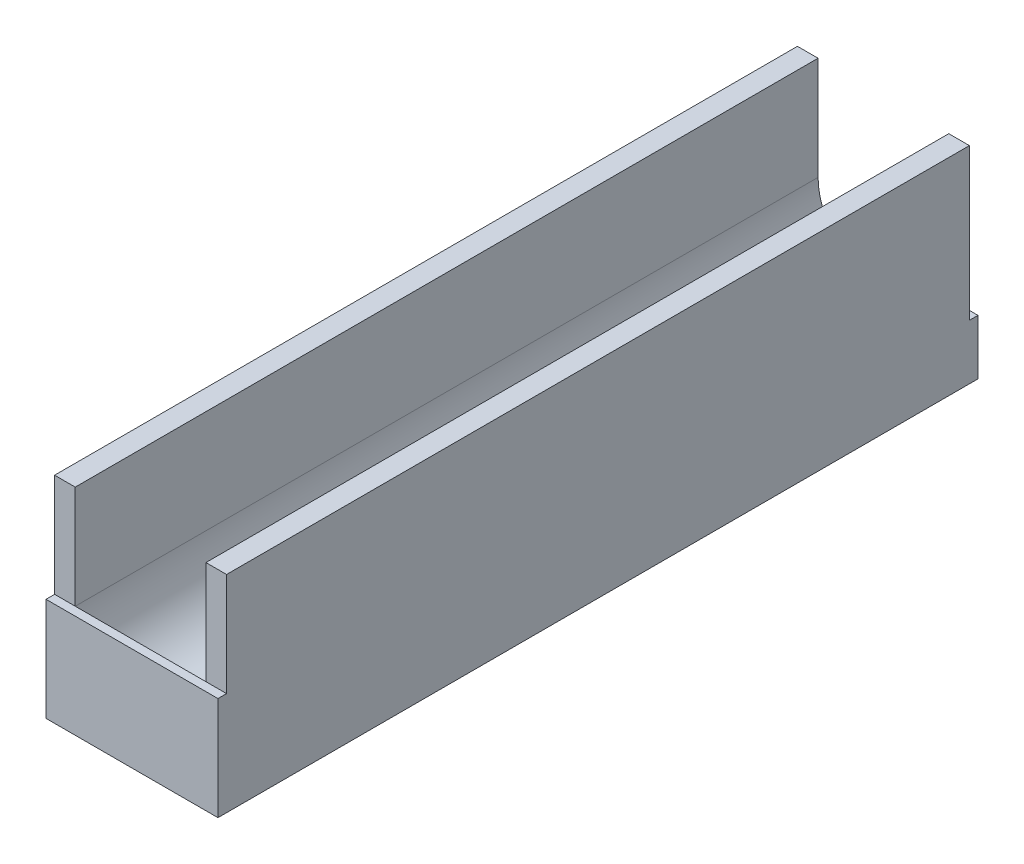
SolidWorks part; units mm, degrees
ref_plane "Front Plane" through (0, 0, 0) normal (0, 0, 1) x (1, 0, 0)
ref_plane "Top Plane" through (0, 0, 0) normal (0, 1, 0) x (1, 0, 0)
ref_plane "Right Plane" through (0, 0, 0) normal (1, 0, 0) x (0, 0, -1)
sketch "Sketch1" plane through (0, 0, 0) normal (0, 0, 1) x (1, 0, 0)
  line L1 (-15.875, 0) -> (15.875, 0)
  line L2 (-15.875, 0) -> (-15.875, 38.1)
  line L3 (-15.875, 38.1) -> (15.875, 38.1)
  line L4 (15.875, 0) -> (15.875, 38.1)
  dimension "D1" = 38.1
  dimension "D2" = 31.75
  dimension "D3" = 15.875
extrude "Boss-Extrude1" add sketch "Sketch1" along normal blind 137.16
sketch "Sketch2" plane through (0, 0, 137.16) normal (0, 0, 1) x (1, 0, 0)
  line L0 (-12.065, 19.05) -> (-12.065, 38.1)
  line L1 (15.875, 38.1) -> (-15.875, 38.1) construction
  line L2 (12.065, 19.05) -> (12.065, 38.1)
  line L3 (12.065, 38.1) -> (-12.065, 38.1)
  arc A2 (-12.065, 19.05) -> (12.065, 19.05) centre (0, 19.05) ccw
  dimension "D1" = 24.13
  dimension "D3" = 19.05
  dimension "D2" = 0
  dimension "D4" = 19.05
extrude "Cut-Extrude1" cut sketch "Sketch2" against normal through all
sketch "Sketch3" plane through (0, 0, 0) normal (0, -1, 0) x (1, 0, 0)
  line L0 (-15.875, 137.16) -> (15.875, 137.16) construction
  line L1 (-15.875, 0) -> (15.875, 0) construction
  circle A0 centre (-12.7, 129.54) radius 2
  circle A1 centre (12.7, 7.62) radius 2
  point P6 (0, 137.16)
  dimension "D1" = 4
  dimension "D2" = 4
  dimension "D6" = 7.62
  dimension "D3" = 12.7
  dimension "D4" = 12.7
  dimension "D5" = 7.62
extrude "heat set insert holes" cut sketch "Sketch3" against normal blind 7
sketch "Sketch4" plane through (0, 0, 137.16) normal (0, 0, 1) x (1, 0, 0)
  line L0 (-15.875, 38.1) -> (-15.875, 0) construction
  line L1 (15.875, 0) -> (-15.875, 0)
  line L2 (15.875, 0) -> (15.875, 19.05)
  line L3 (15.875, 19.05) -> (-15.875, 19.05)
  line L4 (-15.875, 0) -> (-15.875, 19.05)
  dimension "D1" = 19.05
extrude "Boss-Extrude2" add sketch "Sketch4" along normal blind 1.5875
sketch "Sketch5" plane through (0, 0, 0) normal (0, 0, -1) x (-1, 0, 0)
  line L0 (15.875, 38.1) -> (15.875, 0) construction
  line L1 (-15.875, 0) -> (15.875, 0)
  line L2 (-15.875, 0) -> (-15.875, 10.16)
  line L3 (-15.875, 10.16) -> (15.875, 10.16)
  line L4 (15.875, 0) -> (15.875, 10.16)
  dimension "D1" = 10.16
extrude "Boss-Extrude3" add sketch "Sketch5" along normal blind 1.5875
